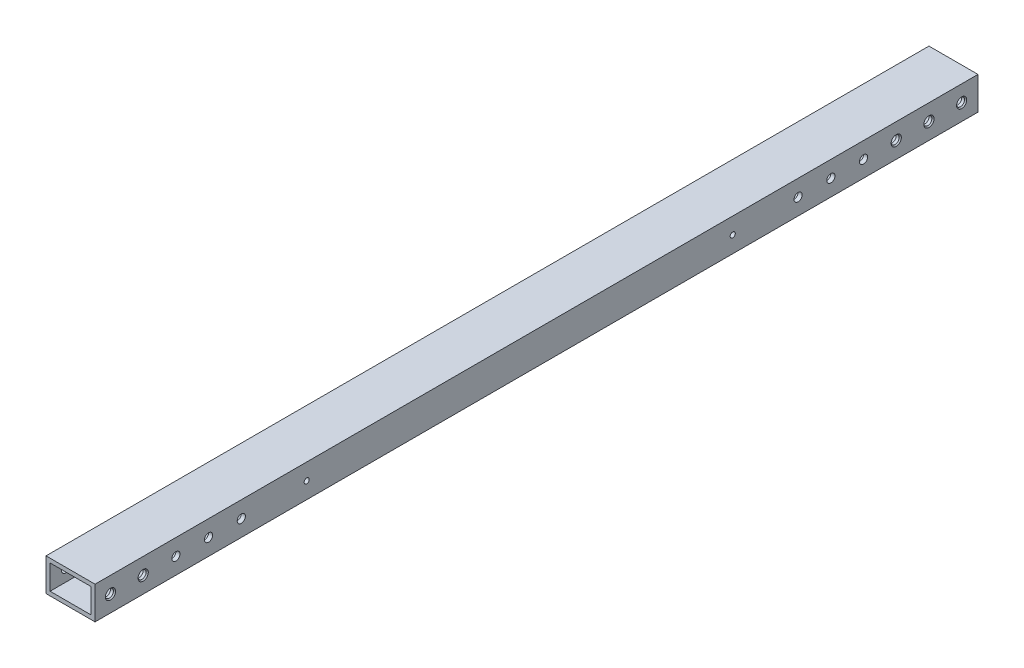
SolidWorks part; units mm, degrees
ref_plane "Front Plane" through (0, 0, 0) normal (0, 0, 1) x (1, 0, 0)
ref_plane "Top Plane" through (0, 0, 0) normal (0, 1, 0) x (1, 0, 0)
ref_plane "Right Plane" through (0, 0, 0) normal (1, 0, 0) x (0, 0, -1)
sketch "Sketch1" plane through (0, 0, 0) normal (0, 0, 1) x (1, 0, 0)
  line L0 (-15.875, 9.525) -> (15.875, 9.525)
  line L2 (-19.05, 12.7) -> (19.05, 12.7)
  line L3 (-19.05, 12.7) -> (-19.05, -12.7)
  line L4 (-19.05, -12.7) -> (19.05, -12.7)
  line L5 (19.05, 12.7) -> (19.05, -12.7)
  line L10 (15.875, 9.525) -> (15.875, -9.525)
  line L11 (-15.875, -9.525) -> (15.875, -9.525)
  line L12 (-15.875, 9.525) -> (-15.875, -9.525)
  point P12 (0, 12.7)
  point P14 (19.05, 0)
  dimension "Wall Thickness" = 3.175
  dimension "Outside Width" = 38.1
  dimension "Outside Height" = 25.4
  dimension "Inside Height" = 19.05
  dimension "Inside Width" = 31.75
sketch "Sketch2" plane through (0, 0, 0) normal (1, 0, 0) x (0, 0, -1)
  line L0 (342.9, 0) -> (-342.9, 0)
  point P4 (0, 0)
  point P7 (-342.9, 0)
  point P10 (342.9, 0)
  dimension "Length" = 685.8
sketch "Sketch3" plane through (0, 0, 0) normal (0, 0, 1) x (1, 0, 0)
  line L21 (19.05, 12.7) -> (-19.05, 12.7)
  line L22 (19.05, -12.7) -> (19.05, 12.7)
  line L23 (-19.05, -12.7) -> (19.05, -12.7)
  line L24 (-19.05, 12.7) -> (-19.05, -12.7)
  line L25 (19.05, 12.7) -> (-19.05, 12.7)
  line L26 (19.05, -12.7) -> (19.05, 12.7)
  line L27 (-19.05, -12.7) -> (19.05, -12.7)
  line L28 (-19.05, 12.7) -> (-19.05, -12.7)
  line L29 (15.875, 9.525) -> (-15.875, 9.525)
  line L30 (15.875, -9.525) -> (15.875, 9.525)
  line L31 (-15.875, -9.525) -> (15.875, -9.525)
  line L32 (-15.875, 9.525) -> (-15.875, -9.525)
  line L33 (15.875, 9.525) -> (-15.875, 9.525)
  line L34 (15.875, -9.525) -> (15.875, 9.525)
  line L35 (-15.875, -9.525) -> (15.875, -9.525)
  line L36 (-15.875, 9.525) -> (-15.875, -9.525)
  dimension "D1" = 0
  dimension "D2" = 0
extrude "Boss-Extrude1" add sketch "Sketch3" along normal up to vertex (342.9 mm away) and the other way up to vertex (342.9 mm away) up to point (0, 0, 342.9) other way up to point (0, 0, -342.9)
sketch "Drawing Reference" plane through (0, 0, 0) normal (1, 0, 0) x (0, 0, -1)
  line L0 (-342.9, 0) -> (342.9, 0) construction
  line L1 (0, -12.7) -> (0, 12.7) construction
  line L2 (-342.9, -12.7) -> (342.9, -12.7) construction
  line L5 (-342.9, 12.7) -> (342.9, 12.7) construction
  point P7 (-315.468, 0)
  point P8 (315.468, 0)
  dimension "D1" = 27.432
sketch "Sketch4" plane through (-19.05, 0, 0) normal (-1, 0, 0) x (0, 0, 1)
  line L0 (-342.9, 0) -> (-330.2, 0)
  line L1 (-342.9, 12.7) -> (-342.9, -12.7) construction
  line L2 (-330.2, 0) -> (-304.8, 0)
  line L3 (-304.8, 0) -> (-279.4, 0)
  line L4 (-279.4, 0) -> (-254, 0)
  line L5 (-254, 0) -> (-228.6, 0)
  line L6 (-228.6, 0) -> (-203.2, 0)
  line L7 (342.9, 0) -> (330.9118, 0)
  line L8 (342.9, 12.7) -> (342.9, -12.7) construction
  line L9 (330.9118, 0) -> (305.5118, 0)
  line L10 (305.5118, 0) -> (280.1118, 0)
  line L11 (280.1118, 0) -> (254.7118, 0)
  line L12 (254.7118, 0) -> (229.3118, 0)
hole_wizard "1/4 (0.25) Diameter Hole2" positions "Sketch7" profile "Sketch8" hole size "1/4" standard "ANSI Inch" end condition through all
sketch "Sketch7" plane through (-19.05, 0, 0) normal (-1, 0, 0) x (0, 0, 1)
  point P0 (-330.2, 0)
  point P3 (-304.8, 0)
  point P7 (330.9118, 0)
  point P11 (-279.4, 0)
  point P14 (305.5118, 0)
sketch "Sketch8" plane through (-19.05, 0, -330.2) normal (0, 1, 0) x (0, 0, 1)
  line L0 (0, 0) -> (0, 38.1)
  line L1 (0, 38.1) -> (3.9624, 38.1)
  line L2 (3.175, 37.1942) -> (3.175, 0)
  line L5 (3.175, 0) -> (0, 0)
  line L7 (3.9624, 38.1) -> (3.175, 37.1942)
  line L8 (-3.9624, 38.1) -> (-3.175, 37.1942) construction
  line L11 (0, -6.35) -> (0, 107.95) construction
  dimension "Thru Hole Dia." = 6.35
  dimension "Thru Hole Depth" = 38.1
  dimension "Far C'Sink Dia." = 7.9248
  dimension "Far C'Sink Angle" = 82
hole_wizard "1/4 (0.25) Diameter Hole3" positions "Sketch9" profile "Sketch10" hole size "1/4" standard "ANSI Inch" end condition through all
sketch "Sketch9" plane through (19.05, 0, 0) normal (1, 0, 0) x (0, 0, -1)
  point P0 (-280.1118, 0)
  point P3 (-254.7118, 0)
  point P6 (-229.3118, 0)
  point P9 (254, 0)
  point P12 (228.6, 0)
  point P15 (203.2, 0)
sketch "Sketch10" plane through (19.05, 0, 280.1118) normal (0, 1, 0) x (0, 0, -1)
  line L0 (0, 0) -> (0, 38.1)
  line L1 (0, 38.1) -> (3.175, 38.1)
  line L2 (3.175, 38.1) -> (3.175, 0)
  line L5 (3.175, 0) -> (0, 0)
  line L11 (0, -6.35) -> (0, 107.95) construction
  dimension "Thru Hole Dia." = 6.35
  dimension "Thru Hole Depth" = 38.1
hole_wizard "5/32 (0.15625) Diameter Hole1" positions "Sketch11" profile "Sketch12" hole size "5/32" standard "ANSI Inch" end condition through all
sketch "Sketch11" plane through (19.05, 0, 0) normal (1, 0, 0) x (0, 0, -1)
  point P0 (152.4, 0)
  point P3 (-178.5118, 0)
sketch "Sketch12" plane through (19.05, 0, -152.4) normal (0, 1, 0) x (0, 0, -1)
  line L0 (0, 0) -> (0, 38.1)
  line L1 (0, 38.1) -> (1.9844, 38.1)
  line L2 (1.9844, 38.1) -> (1.9844, 0)
  line L5 (1.9844, 0) -> (0, 0)
  line L11 (0, -6.35) -> (0, 107.95) construction
  dimension "Thru Hole Dia." = 3.9688
  dimension "Thru Hole Depth" = 38.1
equation "\"D1@Drawing Reference\"=\"Outside Width@Sketch1\" * 0.72"
